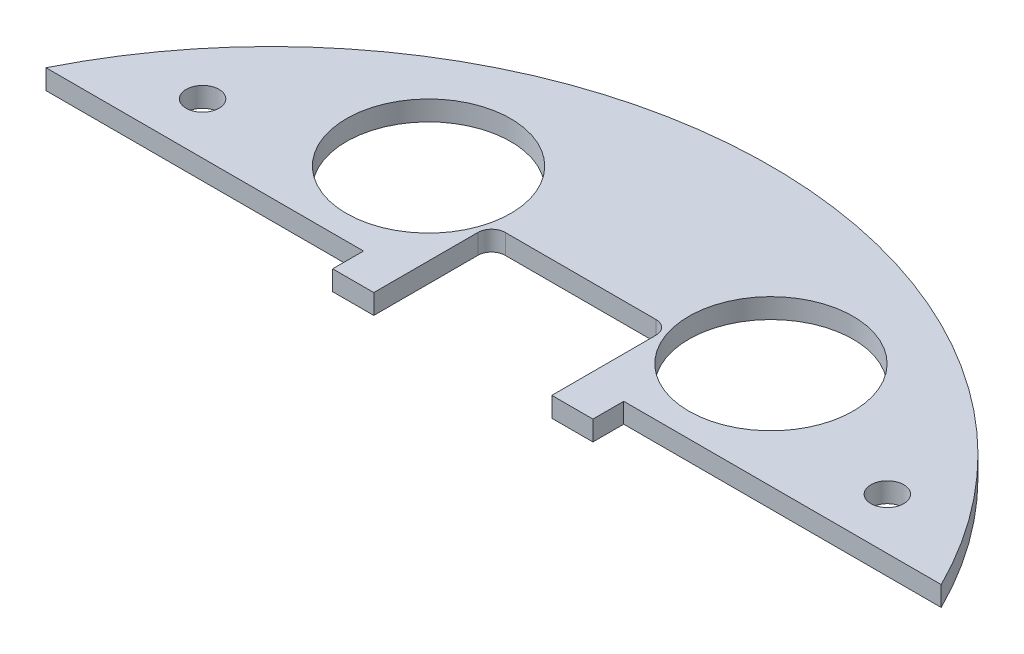
SolidWorks part; units mm, degrees
material "Acrylic (Medium-high impact)"
ref_plane "Front Plane" through (0, 0, 0) normal (0, 0, 1) x (1, 0, 0)
ref_plane "Top Plane" through (0, 0, 0) normal (0, 1, 0) x (1, 0, 0)
ref_plane "Right Plane" through (0, 0, 0) normal (1, 0, 0) x (0, 0, -1)
sketch "Sketch1" plane through (0, 0, 0) normal (0, 1, 0) x (1, 0, 0)
  line L0 (0, -85) -> (-32.7511, -65.2408) construction
  line L1 (0, -85) -> (0, 0) construction
  arc A0 (36.8566, -63.0126) -> (-36.8566, -63.0126) centre (0, 0) ccw
  arc A1 (30.3631, -61.7375) -> (-30.3631, -61.7375) centre (0, -85) ccw
  arc A2 (36.8566, -63.0126) -> (30.3631, -61.7375) centre (34.3322, -58.6967) cw
  arc A3 (-30.3631, -61.7375) -> (-36.8566, -63.0126) centre (-34.3322, -58.6967) cw
  dimension "D1" = 146
  dimension "D2" = 76.5
  dimension "D4" = 5
  dimension "D3" = 85
extrude "Boss-Extrude1" add sketch "Sketch1" along normal blind 2.9
sketch "solenoid placement" plane through (0, 2.9, 0) normal (0, 1, 0) x (1, 0, 0)
  line L4 (-19, -36) -> (19, -36)
  line L5 (-19, 28) -> (-19, -36)
  line L6 (19, 28) -> (-19, 28)
  line L7 (19, -36) -> (19, 28)
  line L8 (-19, -36) -> (19, -36)
  line L9 (-19, 28) -> (-19, -36)
  line L10 (19, 28) -> (-19, 28)
  line L11 (19, -36) -> (19, 28)
  dimension "D1" = 0
extrude "Cut-Extrude1" cut sketch "solenoid placement" against normal through all
sketch "Sketch4" plane through (0, 2.9, 0) normal (0, 1, 0) x (1, 0, 0)
  line L6 (-13, 28) -> (13, 28)
  line L7 (13, 28) -> (13, 43.2)
  line L8 (11, 45.2) -> (-11, 45.2)
  line L9 (-13, 43.2) -> (-13, 28)
  line L10 (-13, 28) -> (13, 28)
  line L11 (13, 28) -> (13, 43.2)
  line L12 (11, 45.2) -> (-11, 45.2)
  line L13 (-13, 43.2) -> (-13, 28)
  arc A4 (13, 43.2) -> (11, 45.2) centre (11, 43.2) ccw
  arc A5 (13, 43.2) -> (11, 45.2) centre (11, 43.2) ccw
  arc A6 (-11, 45.2) -> (-13, 43.2) centre (-11, 43.2) ccw
  arc A7 (-11, 45.2) -> (-13, 43.2) centre (-11, 43.2) ccw
  dimension "D1" = 0
extrude "Cut-Extrude4" cut sketch "Sketch4" against normal through all
sketch "Sketch5" plane through (0, 2.9, 0) normal (0, 1, 0) x (1, 0, 0)
  circle A1 centre (25, 48) radius 12
  circle A2 centre (25, 48) radius 12
  circle A3 centre (-25, 48) radius 12
  circle A4 centre (-25, 48) radius 12
  dimension "D1" = 0
  dimension "D2" = 0
extrude "Cut-Extrude5" cut sketch "Sketch5" against normal through all
sketch "Sketch6" plane through (0, 2.9, 0) normal (0, 1, 0) x (1, 0, 0)
  circle A1 centre (40, -40) radius 2.4
  circle A2 centre (40, -40) radius 2.4
  circle A3 centre (-40, -40) radius 2.4
  circle A4 centre (-40, -40) radius 2.4
  circle A5 centre (-50, 40) radius 2.4
  circle A6 centre (-50, 40) radius 2.4
  circle A7 centre (50, 40) radius 2.4
  circle A8 centre (50, 40) radius 2.4
  dimension "D1" = 0
  dimension "D2" = 0
  dimension "D3" = 0
  dimension "D4" = 0
extrude "Cut-Extrude6" cut sketch "Sketch6" against normal through all
sketch "Sketch7" plane through (0, 2.9, 0) normal (0, 1, 0) x (1, 0, 0)
  line L1 (-5, 0) -> (5, 0)
  line L2 (-5, 0) -> (-5, -62.8025)
  line L3 (-5, -62.8025) -> (5, -62.8025)
  line L4 (5, 0) -> (5, -62.8025)
  dimension "D1" = 10
extrude "Cut-Extrude7" cut sketch "Sketch7" against normal through all
sketch "Sketch3" plane through (0, 2.9, 0) normal (0, 1, 0) x (1, 0, 0)
  line L0 (-19, 28) -> (19, 28)
  line L1 (-73, -32.5) -> (73, -32.5)
  line L2 (-73, -32.5) -> (-73, 32.5)
  line L3 (-73, 32.5) -> (-19, 32.5)
  line L4 (73, -32.5) -> (73, 32.5)
  line L5 (-73, -32.5) -> (73, 32.5) construction
  line L6 (-73, 32.5) -> (73, -32.5) construction
  line L7 (19, 28) -> (19, 32.5)
  line L8 (-19, 28) -> (-19, 32.5)
  line L9 (19, 32.5) -> (73, 32.5)
  arc A0 (36.8566, -63.0126) -> (-36.8566, -63.0126) centre (0, 0) ccw construction
  point P0 (0, 0)
  dimension "D1" = 65
extrude "Cut-Extrude3" cut sketch "Sketch3" against normal through all
delete or keep bodies "Body-Delete/Keep 1" type delete bodies bodies 116 119
equation "\"smallPulleyTeeth\"= 15"
equation "\"largePulleyTeeth\"= 30"
equation "\"eighthThick\"= 2.9mm"
equation "\"sixteenthThick\" = 1.7mm"
equation "\"quarterThick\"=6.0mm"
equation "\"OD\" = 146mm"
equation "\"puckAngle\" = 60.5deg"
equation "\"D1@Sketch1\"=\"OD\""
equation "\"puckDiam\" = 76.5mm"
equation "\"D2@Sketch1\"=\"puckDiam\""
equation "\"D1@Boss-Extrude1\"=\"eighthThick\""
equation "\"axlePress\" = 5.9mm"
equation "\"press\" = 0.2mm"
equation "\"wheelClear\" = 0.3mm"
equation "\"10-32clear\" = 4.8mm"
equation "\"6-32clear\" = 3.3mm"
equation "\"8-32clear\" = 4.0mm"
equation "\"wheelHeight\" = 22mm"
equation "\"wheelWell\" = 65mm"
equation "\"D1@Sketch3\"=\"wheelWell\""
equation "\"puckDist\" = 85mm"
equation "\"scoopFillet\" = 5mm"
equation "\"4-40clear\" = 3.0mm"
equation "\"D3@Sketch1\"=\"puckDist\""
equation "\"D4@Sketch1\"=\"scoopFillet\""
